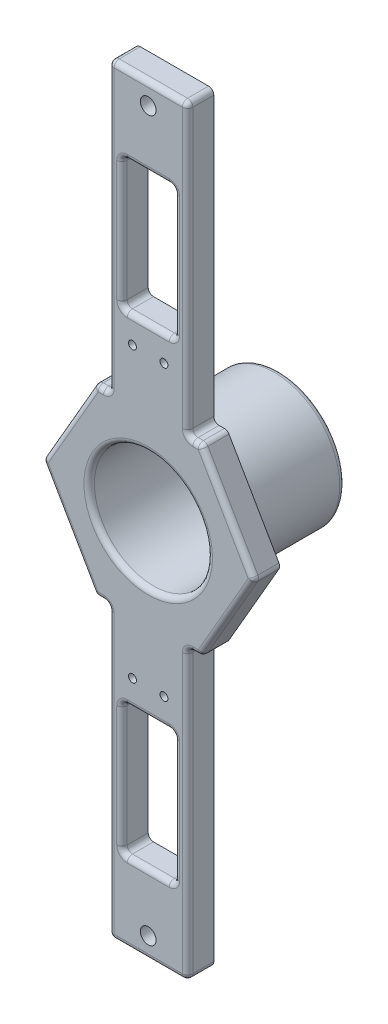
SolidWorks part; units mm, degrees
ref_plane "Спереди" through (0, 0, 0) normal (0, 0, 1) x (1, 0, 0)
ref_plane "Сверху" through (0, 0, 0) normal (0, 1, 0) x (1, 0, 0)
ref_plane "Справа" through (0, 0, 0) normal (1, 0, 0) x (0, 0, -1)
other "Configuration Table"
sketch "Sketch1" plane through (0, 0, 0) normal (0, 0, 1) x (1, 0, 0)
  line L1 (20.2073, 35) -> (-20.2073, 35)
  line L2 (-20.2073, 35) -> (-40.4145, 0)
  line L3 (-40.4145, 0) -> (-20.2073, -35)
  line L4 (-20.2073, -35) -> (20.2073, -35)
  line L5 (20.2073, -35) -> (40.4145, 0)
  line L6 (40.4145, 0) -> (20.2073, 35)
  circle A1 centre (0, 0) radius 35 construction
  dimension "D1" = 70
extrude "Boss-Extrude2" add sketch "Sketch1" along normal blind 10
sketch "Sketch4" plane through (0, 0, 0) normal (0, 0, -1) x (-1, 0, 0)
  line L0 (0, 0) -> (0, 40.6349) construction
  line L1 (-56.6567, 0) -> (54.1025, 0) construction
  line L2 (-20.2073, 35) -> (20.2073, 35) construction
  line L3 (-15, 35) -> (15, 35)
  line L4 (-15, 35) -> (-15, 145)
  line L5 (-15, 145) -> (15, 145)
  line L6 (15, 35) -> (15, 145)
  line L7 (-15, -145) -> (15, -145)
  line L8 (15, -35) -> (15, -145)
  line L9 (-15, -35) -> (15, -35)
  line L10 (-15, -35) -> (-15, -145)
  line L11 (0, 145) -> (0, 121.9848) construction
  circle A0 centre (0, 137) radius 1.5
  circle A1 centre (0, -137) radius 1.5
  dimension "D3" = 3
  dimension "D1" = 30
  dimension "D2" = 110
  dimension "D4" = 137
extrude "Boss-Extrude4" add sketch "Sketch4" against normal up to surface (10 mm away) up to face at (0, 0, 10)
sketch "Sketch5" plane through (0, 0, 10) normal (0, 0, 1) x (1, 0, 0)
  circle A0 centre (0, 137) radius 3
  circle A1 centre (0, -137) radius 3
  dimension "D1" = 6
  dimension "D2" = 6
extrude "Cut-Extrude3" cut sketch "Sketch5" against normal blind 5
sketch "Sketch6" plane through (0, 0, 0) normal (0, 0, -1) x (-1, 0, 0)
  line L0 (-44.6052, 0) -> (88.3819, 0) construction
  line L1 (0, 145) -> (0, 120.7707) construction
  line L2 (15, 145) -> (-15, 145) construction
  line L3 (0, 137) -> (-4.1294, 137) construction
  line L4 (3, 138) -> (7, 138)
  line L5 (-1, 140) -> (1, 140)
  line L6 (-1, 140) -> (-1, 144)
  line L7 (-1, 144) -> (1, 144)
  line L8 (1, 140) -> (1, 144)
  line L9 (-1, 140) -> (1, 144) construction
  line L10 (-1, 144) -> (1, 140) construction
  line L11 (3, 138) -> (3, 136)
  line L12 (3, 136) -> (7, 136)
  line L13 (7, 138) -> (7, 136)
  line L14 (1, 134) -> (1, 130)
  line L15 (1, 134) -> (-1, 134)
  line L16 (-1, 134) -> (-1, 130)
  line L17 (1, 130) -> (-1, 130)
  line L18 (-3, 136) -> (-7, 136)
  line L19 (-3, 136) -> (-3, 138)
  line L20 (-3, 138) -> (-7, 138)
  line L21 (-7, 136) -> (-7, 138)
  line L22 (1, -134) -> (-1, -134)
  line L23 (-1, -134) -> (-1, -130)
  line L24 (1, -130) -> (-1, -130)
  line L25 (1, -134) -> (1, -130)
  line L26 (3, -138) -> (3, -136)
  line L27 (3, -136) -> (7, -136)
  line L28 (7, -138) -> (7, -136)
  line L29 (3, -138) -> (7, -138)
  line L30 (-3, -136) -> (-3, -138)
  line L31 (-3, -138) -> (-7, -138)
  line L32 (-7, -136) -> (-7, -138)
  line L33 (-3, -136) -> (-7, -136)
  line L34 (-1, -144) -> (1, -144)
  line L35 (1, -140) -> (1, -144)
  line L36 (-1, -140) -> (1, -140)
  line L37 (-1, -140) -> (-1, -144)
  point P10 (0, 142)
  point P31 (0, 137)
  dimension "D1" = 4
  dimension "D2" = 2
  dimension "D3" = 3
  dimension "D4" = 4
extrude "Cut-Extrude4" cut sketch "Sketch6" against normal blind 4
sketch "Sketch13" plane through (0, 0, 10) normal (0, 0, 1) x (1, 0, 0)
  line L0 (15, 145) -> (15, 35) construction
  line L1 (10, 65) -> (-10, 65)
  line L2 (10, 65) -> (10, 115)
  line L3 (10, 115) -> (-10, 115)
  line L4 (-10, 65) -> (-10, 115)
  line L5 (10, 65) -> (-10, 115) construction
  line L6 (10, 115) -> (-10, 65) construction
  line L7 (0, 145) -> (0, 62.8418) construction
  line L8 (-15, 145) -> (15, 145) construction
  line L9 (-15, 90) -> (15, 90) construction
  line L10 (-15, 35) -> (-15, 145) construction
  line L11 (-40.4145, 0) -> (62.8003, 0) construction
  line L12 (10, -115) -> (-10, -115)
  line L13 (-10, -65) -> (-10, -115)
  line L14 (10, -65) -> (-10, -65)
  line L15 (10, -65) -> (10, -115)
  point P0 (0, 90)
  dimension "D1" = 5
  dimension "D2" = 50
extrude "Cut-Extrude7" cut sketch "Sketch13" against normal up to next
fillet "Fillet4" radius 2 44 edges at (15, 90, 10) (0, 145, 10) (-15, 90, 10) (-30.3109, 17.5, 10) (-30.3109, -17.5, 10) (15, -90, 10) (30.3109, 17.5, 10) (-15, -90, 10) (0, -145, 10) (30.3109, -17.5, 10) (17.6036, 35, 10) (17.6036, -35, 10) (-17.6036, -35, 10) (-17.6036, 35, 10) (10, -65, 5) (-10, -65, 5) (-10, -115, 5) (10, -115, 5) (-10, 65, 5) (-10, 115, 5) (10, 115, 5) (10, 65, 5) (40.4145, 0, 5) (20.2073, -35, 5) (15, -35, 5) (15, -145, 5) (-15, -145, 5) (-15, -35, 5) (-20.2073, -35, 5) (-40.4145, 0, 5) (-20.2073, 35, 5) (-15, 35, 5) (15, 145, 5) (15, 35, 5) (20.2073, 35, 5) (-15, 145, 5) (0, -115, 10) (0, 115, 10) (10, -90, 10) (-10, -90, 10) (-10, 90, 10) (10, 90, 10) (0, -65, 10) (0, 65, 10)
sketch "Sketch14" plane through (0, 0, 0) normal (0, 0, -1) x (-1, 0, 0)
  circle A0 centre (0, 0) radius 25
  dimension "D1" = 50
extrude "Boss-Extrude5" add sketch "Sketch14" along normal blind 40
sketch "Sketch15" plane through (0, 0, 10) normal (0, 0, 1) x (1, 0, 0)
  circle A0 centre (0, 0) radius 22.5
  dimension "D1" = 45
extrude "Cut-Extrude8" cut sketch "Sketch15" against normal offset from surface (45 mm away) 5 up to face at (-25, 0, -40)
sketch "Sketch16" plane through (0, 0, -40) normal (0, 0, -1) x (-1, 0, 0)
  circle A0 centre (0, 0) radius 9
  dimension "D1" = 18
extrude "Cut-Extrude9" cut sketch "Sketch16" against normal up to next
sketch "Sketch17" plane through (0, 0, -40) normal (0, 0, -1) x (-1, 0, 0)
  line L0 (-44.5312, 0) -> (54.6996, 0) construction
  line L1 (0, 0) -> (0, 13.5892) construction
  circle A0 centre (-14.5, 0) radius 2
  circle A1 centre (14.5, 0) radius 2
  dimension "D1" = 4
  dimension "D2" = 29
extrude "Cut-Extrude10" cut sketch "Sketch17" against normal up to next
fillet "Fillet5" radius 2 1 edges at (-25, 0, -40)
fillet "Fillet6" radius 2 1 edges at (22.5, 0, 10)
sketch "Sketch18" plane through (0, 0, -40) normal (0, 0, -1) x (-1, 0, 0)
  line L0 (0, 0) -> (24.123, 24.123) construction
  line L1 (7.5831, 14.6542) -> (0, 0) construction
  line L2 (0, 0) -> (14.6542, 7.5831) construction
  line L3 (14.6542, 7.5831) -> (11.1017, 5.7448)
  line L4 (7.5831, 14.6542) -> (5.7448, 11.1017)
  line L5 (0, 0) -> (49.2355, 0) construction
  line L6 (14.6542, -7.5831) -> (11.1017, -5.7448)
  line L7 (7.5831, -14.6542) -> (5.7448, -11.1017)
  line L8 (-7.5831, -14.6542) -> (-5.7448, -11.1017)
  line L9 (-14.6542, -7.5831) -> (-11.1017, -5.7448)
  line L10 (-14.6542, 7.5831) -> (-11.1017, 5.7448)
  line L11 (-7.5831, 14.6542) -> (-5.7448, 11.1017)
  arc A0 (7.5831, 14.6542) -> (14.6542, 7.5831) centre (0, 0) cw
  arc A1 (5.7448, 11.1017) -> (11.1017, 5.7448) centre (0, 0) cw
  arc A2 (11.1017, -5.7448) -> (5.7448, -11.1017) centre (0, 0) cw
  arc A3 (14.6542, -7.5831) -> (7.5831, -14.6542) centre (0, 0) cw
  arc A4 (-5.7448, -11.1017) -> (-11.1017, -5.7448) centre (0, 0) cw
  arc A5 (-7.5831, -14.6542) -> (-14.6542, -7.5831) centre (0, 0) cw
  arc A6 (-11.1017, 5.7448) -> (-5.7448, 11.1017) centre (0, 0) cw
  arc A7 (-14.6542, 7.5831) -> (-7.5831, 14.6542) centre (0, 0) cw
  point P23 (0, 0)
  dimension "D1" = 16.5
  dimension "D2" = 12.5
  dimension "D3" = 10
  dimension "D4" = 45
  dimension "D5" = 4
extrude "Cut-Extrude11" cut sketch "Sketch18" against normal up to next
sketch "Sketch19" plane through (0, 0, 10) normal (0, 0, 1) x (1, 0, 0)
  line L0 (-54.9132, 0) -> (94.5139, 0) construction
  line L1 (-6, 55) -> (6, 55) construction
  line L2 (0, 0) -> (0, 76.9882) construction
  circle A0 centre (-6, 55) radius 1.5
  circle A1 centre (6, 55) radius 1.5
  circle A2 centre (6, -55) radius 1.5
  circle A3 centre (-6, -55) radius 1.5
  dimension "D1" = 3
  dimension "D2" = 12
  dimension "D3" = 110
extrude "Cut-Extrude12" cut sketch "Sketch19" against normal up to next
sketch "Sketch20" plane through (0, 0, 0) normal (0, 0, -1) x (-1, 0, 0)
  circle A0 centre (-6, -55) radius 3
  circle A1 centre (6, -55) radius 3
  circle A2 centre (-6, 55) radius 3
  circle A3 centre (6, 55) radius 3
  dimension "D1" = 6
extrude "Cut-Extrude13" cut sketch "Sketch20" against normal blind 5
